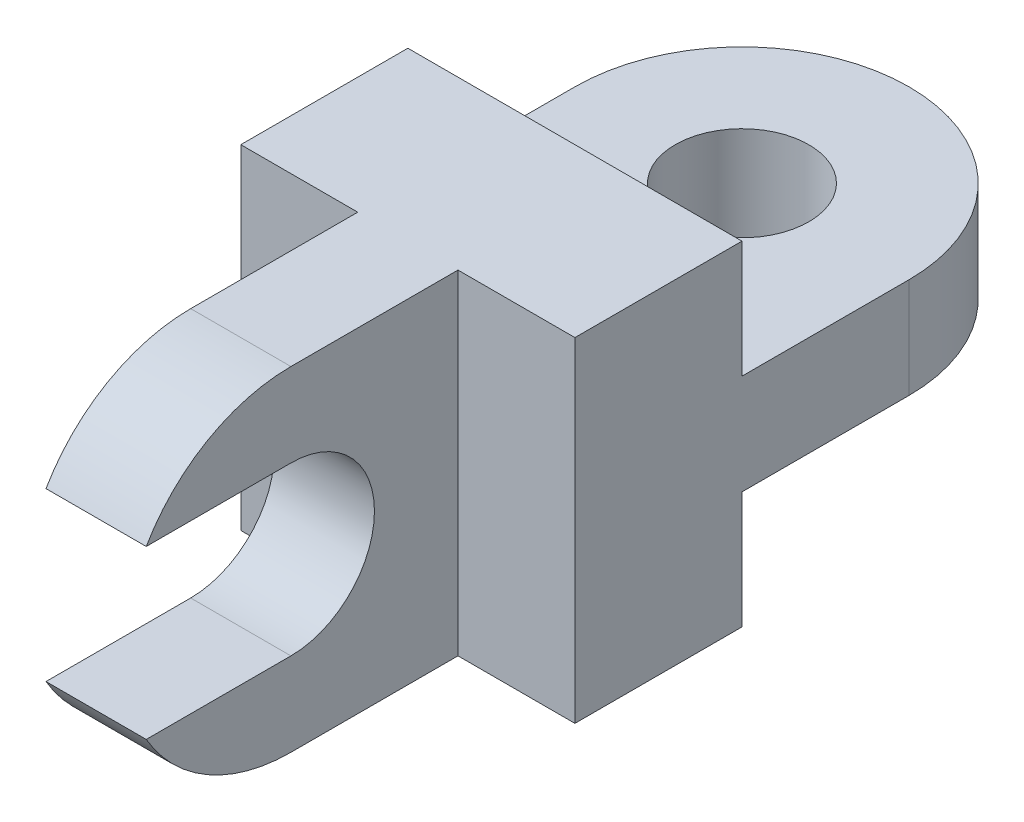
SolidWorks part; units mm, degrees
ref_plane "Alzado" through (0, 0, 0) normal (0, 0, 1) x (1, 0, 0)
ref_plane "Planta" through (0, 0, 0) normal (0, 1, 0) x (1, 0, 0)
ref_plane "Vista lateral" through (0, 0, 0) normal (1, 0, 0) x (0, 0, -1)
sketch "Croquis3" plane through (0, 0, 0) normal (0, 1, 0) x (1, 0, 0)
  line L0 (-50, 0) -> (-50, -50)
  line L1 (-50, -50) -> (50, -50)
  line L2 (50, -50) -> (50, 0)
  line L3 (0, 0) -> (0, 50) construction
  arc A0 (50, 0) -> (-50, 0) centre (0, 0) ccw
  circle A1 centre (0, 0) radius 20
  dimension "D1" = 100
  dimension "D3" = 40
  dimension "D2" = 100
extrude "Saliente-Extruir1" add sketch "Croquis3" along normal blind 30
sketch "Croquis4" plane through (0, 0, 0) normal (0, 1, 0) x (1, 0, 0)
  line L0 (-50, -50) -> (-50, -100)
  line L1 (-50, -100) -> (50, -100)
  line L2 (50, -100) -> (50, -50)
  line L6 (-50, 0) -> (-50, -50)
  line L7 (-50, -50) -> (50, -50)
  line L8 (50, -50) -> (50, 0)
  line L10 (-50, -50) -> (50, -50)
  arc A1 (50, 0) -> (-50, 0) centre (0, 0) ccw
  dimension "D1" = 100
  dimension "D2" = 0
extrude "Saliente-Extruir2" add sketch "Croquis4" along normal blind 65
sketch "Croquis5" plane through (0, 0, 0) normal (0, -1, 0) x (1, 0, 0)
  line L0 (-50, 0) -> (-50, 100) construction
  line L1 (50, 100) -> (-50, 100)
  line L2 (50, 100) -> (50, 50)
  line L3 (50, 50) -> (-50, 50)
  line L4 (-50, 100) -> (-50, 50)
extrude "Saliente-Extruir3" add sketch "Croquis5" along normal blind 35
sketch "Croquis6" plane through (0, 0, 0) normal (1, 0, 0) x (0, 0, -1)
  line L0 (-100, 65) -> (-193.3, 65)
  line L1 (-100, -35) -> (-100, 15) construction
  line L2 (-100, 65) -> (-100, -35) construction
  line L3 (-150, 40) -> (-193.3, 40)
  line L4 (-193.3, 40) -> (-193.3, 65)
  line L5 (50, 0) -> (50, 30) construction
  line L6 (-150, -10) -> (-193.3, -10)
  line L7 (-193.3, -10) -> (-193.3, -35)
  line L8 (-193.3, -35) -> (-100, -35)
  line L9 (-100, -35) -> (-100, 65)
  arc A0 (-150, -10) -> (-150, 40) centre (-150, 15) ccw
  dimension "D1" = 50
  dimension "D2" = 193.3
  dimension "D3" = 200
extrude "Saliente-Extruir4" add sketch "Croquis6" along normal blind 15 and the other way blind 15
fillet "Redondeo2" radius 50 2 edges at (0, -35, 193.3) (0, 65, 193.3)
